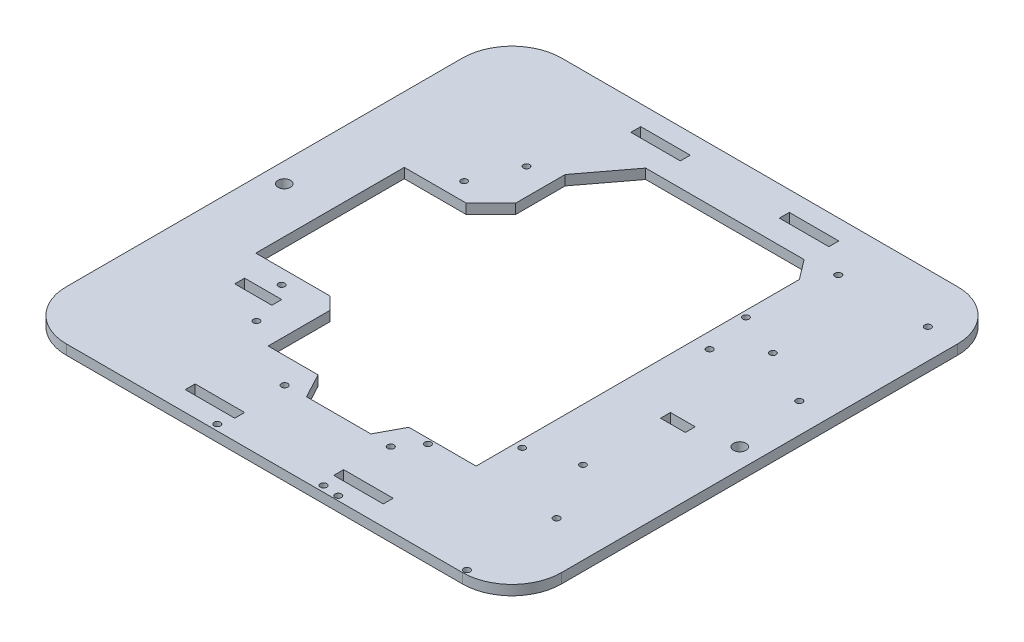
SolidWorks part; units mm, degrees
ref_plane "Front Plane" through (0, 0, 0) normal (0, 0, 1) x (1, 0, 0)
ref_plane "Top Plane" through (0, 0, 0) normal (0, 1, 0) x (1, 0, 0)
ref_plane "Right Plane" through (0, 0, 0) normal (1, 0, 0) x (0, 0, -1)
sketch "Sketch1" plane through (0, 0, 0) normal (0, 1, 0) x (1, 0, 0)
  line L1 (-127, -127) -> (127, -127)
  line L2 (-127, -127) -> (-127, 127)
  line L3 (-127, 127) -> (127, 127)
  line L4 (127, -127) -> (127, 127)
  line L5 (-127, -127) -> (127, 127) construction
  line L6 (-127, 127) -> (127, -127) construction
  point P0 (0, 0)
  dimension "D1" = 254
  dimension "D2" = 254
extrude "Platform-Base" add sketch "Sketch1" along normal blind 5.08
ref_axis "Axis1" through (-127, 5.08, 0) along (0, -1, 0)
ref_plane "Plane1" through (0, 0, 0) normal (0, 0, 1) x (0, -1, 0)
sketch "Sketch5" plane through (0, 5.08, 0) normal (0, 1, 0) x (1, 0, 0)
  line L0 (127, 0) -> (0, 0) construction
  line L1 (127, -127) -> (127, 127) construction
  line L3 (48.895, 76.2) -> (-48.895, 76.2)
  line L4 (48.895, 76.2) -> (48.895, -76.2)
  line L5 (48.895, -76.2) -> (-48.895, -76.2)
  line L6 (-48.895, 76.2) -> (-48.895, -76.2)
  line L7 (48.895, 76.2) -> (-48.895, -76.2) construction
  line L8 (48.895, -76.2) -> (-48.895, 76.2) construction
  dimension "D1" = 127
  dimension "D2" = 97.79
  dimension "D3" = 152.4
extrude "Cut-Extrude3" cut sketch "Sketch5" against normal through all
sketch "Sketch6" plane through (0, 5.08, 0) normal (0, 1, 0) x (1, 0, 0)
  line L2 (25.4, -116.84) -> (25.4, -127) construction
  line L3 (-127, -127) -> (127, -127) construction
  line L4 (50.8, -116.84) -> (127, -116.84) construction
  line L5 (25.4, -116.84) -> (50.8, -116.84)
  line L6 (25.4, -116.84) -> (25.4, -111.76)
  line L7 (25.4, -111.76) -> (50.8, -111.76)
  line L8 (50.8, -116.84) -> (50.8, -111.76)
  line L9 (127, -127) -> (127, 127) construction
  dimension "D2" = 10.16
  dimension "D3" = 5.08
extrude "Cut-Extrude4" cut sketch "Sketch6" against normal through all
mirror "Mirror4" about plane through (0, 0, 0) normal (0, 0, 1) of "Cut-Extrude4"
fillet "Corner-Rounding" radius 25.4 4 edges at (-127, 2.54, -127) (127, 2.54, -127) (127, 2.54, 127) (-127, 2.54, 127)
ref_axis "Axis2" through (0, 5.08, 127) along (0, -1, 0)
ref_plane "Plane2" through (0, 0, 0) normal (-1, 0, 0) x (0, -1, 0)
mirror "Mirror6" about plane through (0, 0, 0) normal (-1, 0, 0) of "Mirror4"
sketch "Sketch7" plane through (0, 5.08, 0) normal (0, 1, 0) x (1, 0, 0)
  line L0 (127, 0) -> (116.84, 0) construction
  line L1 (127, -101.6) -> (127, 101.6) construction
  circle A0 centre (116.84, 0) radius 3.175
  dimension "D1" = 6.35
  dimension "D2" = 10.16
extrude "Cut-Extrude5" cut sketch "Sketch7" against normal through all
mirror "Mirror7" about plane through (0, 0, 0) normal (-1, 0, 0) of "Cut-Extrude5"
sketch "Sketch11" plane through (0, 5.08, 0) normal (0, 1, 0) x (1, 0, 0)
  line L0 (127, -5.08) -> (127, 0) construction
  line L1 (127, -101.6) -> (127, 101.6) construction
  line L2 (127, -5.08) -> (90.17, -5.08) construction
  line L4 (83.82, -7.62) -> (96.52, -7.62)
  line L5 (83.82, -7.62) -> (83.82, -2.54)
  line L6 (83.82, -2.54) -> (96.52, -2.54)
  line L7 (96.52, -7.62) -> (96.52, -2.54)
  line L8 (83.82, -7.62) -> (96.52, -2.54) construction
  line L9 (83.82, -2.54) -> (96.52, -7.62) construction
  dimension "D3" = 5.08
  dimension "D2" = 36.83
extrude "Cut-Extrude8" cut sketch "Sketch11" against normal through all
sketch "Sketch12" plane through (0, 5.08, 0) normal (0, 1, 0) x (1, 0, 0)
  line L0 (-66.04, -127) -> (-66.04, -57.15) construction
  line L1 (-101.6, -127) -> (101.6, -127) construction
  line L2 (-66.04, -57.15) -> (-127, -57.15) construction
  line L3 (-127, 101.6) -> (-127, -101.6) construction
  line L5 (-66.04, -57.15) -> (-85.09, -57.15)
  line L6 (-66.04, -57.15) -> (-66.04, -52.07)
  line L7 (-66.04, -52.07) -> (-85.09, -52.07)
  line L8 (-85.09, -57.15) -> (-85.09, -52.07)
  dimension "D1" = 69.85
  dimension "D2" = 60.96
  dimension "D3" = 19.05
  dimension "D4" = 5.08
extrude "Cut-Extrude10" cut sketch "Sketch12" against normal blind 16.51
sketch "Sketch14" plane through (48.895, 0, 0) normal (-1, 0, 0) x (0, 0, 1)
  line L0 (0, 5.08) -> (0, 2.1293) construction
  line L1 (76.2, 5.08) -> (-76.2, 5.08) construction
  line L3 (-76.2, -0.4107) -> (76.2, -0.4107)
  line L4 (-76.2, -0.4107) -> (-76.2, 7.62)
  line L5 (-76.2, 7.62) -> (76.2, 7.62)
  line L6 (76.2, -0.4107) -> (76.2, 7.62)
  line L7 (-76.2, -0.4107) -> (76.2, 7.62) construction
  line L8 (-76.2, 7.62) -> (76.2, -0.4107) construction
  point P5 (0, 3.6047)
  dimension "D1" = 152.4
extrude "Cut-Extrude12" cut sketch "Sketch14" against normal blind 19.05
sketch "Sketch16" plane through (-48.895, 0, 0) normal (1, 0, 0) x (0, 0, -1)
  line L0 (0, 5.08) -> (0, 0) construction
  line L1 (76.2, 5.08) -> (-76.2, 5.08) construction
  line L2 (76.2, 0) -> (-76.2, 0) construction
  line L4 (-38.1, 5.08) -> (38.1, 5.08)
  line L5 (-38.1, 5.08) -> (-38.1, 0)
  line L6 (-38.1, 0) -> (38.1, 0)
  line L7 (38.1, 5.08) -> (38.1, 0)
  line L8 (-38.1, 5.08) -> (38.1, 0) construction
  line L9 (-38.1, 0) -> (38.1, 5.08) construction
  point P6 (0, 2.54)
  dimension "D1" = 76.2
extrude "Cut-Extrude14" cut sketch "Sketch16" against normal blind 44.45
sketch "Sketch18" plane through (0, 5.08, 0) normal (0, 1, 0) x (1, 0, 0)
  line L6 (-48.895, 76.2) -> (-26.6168, 34.3809)
  line L8 (-48.895, 76.2) -> (-31.115, 99.6865)
  line L9 (-31.115, 99.6865) -> (50.165, 99.6865)
  line L10 (67.945, 76.2) -> (50.165, 99.6865)
  line L11 (101.6, 127) -> (-101.6, 127) construction
  line L12 (-26.6168, 34.3809) -> (67.945, 76.2)
  dimension "D1" = 81.28
extrude "Cut-Extrude16" cut sketch "Sketch18" against normal through all
sketch "Sketch20" plane through (0, 5.08, 0) normal (0, 1, 0) x (1, 0, 0)
  line L0 (-48.895, 38.1) -> (-48.895, 50.8)
  line L1 (-48.895, 76.2) -> (-48.895, 38.1) construction
  line L2 (-48.895, 50.8) -> (-61.595, 38.1)
  line L3 (-93.345, 38.1) -> (-48.895, 38.1) construction
  line L4 (-61.595, 38.1) -> (-48.895, 38.1)
  dimension "D1" = 12.7
extrude "Cut-Extrude18" cut sketch "Sketch20" against normal through all
sketch "Sketch21" plane through (0, 5.08, 0) normal (0, 1, 0) x (1, 0, 0)
  line L0 (-48.895, -38.1) -> (-48.895, -44.45)
  line L1 (-48.895, -38.1) -> (-48.895, -76.2) construction
  line L2 (-48.895, -44.45) -> (-55.245, -38.1)
  line L3 (-93.345, -38.1) -> (-48.895, -38.1) construction
  line L4 (-55.245, -38.1) -> (-48.895, -38.1)
  dimension "D1" = 6.35
extrude "Cut-Extrude19" cut sketch "Sketch21" against normal through all
sketch "Sketch22" plane through (0, 5.08, 0) normal (0, 1, 0) x (1, 0, 0)
  line L0 (-25.4, -111.76) -> (25.4, -111.76) construction
  line L1 (25.4, -111.76) -> (25.4, -116.84) construction
  line L2 (50.8, -111.76) -> (25.4, -111.76) construction
  line L3 (0, -111.76) -> (0, -88.9) construction
  line L4 (0, -88.9) -> (16.51, -88.9)
  line L5 (16.51, -88.9) -> (23.2939, -76.2)
  line L6 (-48.895, -76.2) -> (67.945, -76.2) construction
  line L7 (0, -88.9) -> (-16.51, -88.9)
  line L8 (-16.51, -88.9) -> (-23.2939, -76.2)
  line L9 (-23.2939, -76.2) -> (-5.6383, -47.7846)
  line L10 (-5.6383, -47.7846) -> (23.2939, -76.2)
  dimension "D1" = 22.86
  dimension "D2" = 16.51
extrude "Cut-Extrude20" cut sketch "Sketch22" against normal through all
sketch "Sketch27" plane through (0, 0, 76.2) normal (0, 0, -1) x (-1, 0, 0)
  line L0 (-23.2939, 5.08) -> (-67.945, 5.08) construction
  line L1 (-57.785, 5.08) -> (-67.945, 5.08)
  line L2 (-57.785, 5.08) -> (-57.785, 0)
  line L3 (-57.785, 0) -> (-67.945, 0)
  line L4 (-67.945, 5.08) -> (-67.945, 0)
  dimension "D1" = 10.16
extrude "Boss-Extrude1" add sketch "Sketch27" along normal blind 177.8
sketch "Sketch28" plane through (0, 0, 0) normal (0, -1, 0) x (1, 0, 0)
  circle A0 centre (-62.9935, 68.1005) radius 1.6
  circle A1 centre (-72.5993, 45.5914) radius 1.6
  circle A2 centre (-71.8559, -47.2939) radius 1.6
  circle A3 centre (-62.447, -69.886) radius 1.6
  circle A4 centre (60.9077, -59.1041) radius 1.6
  circle A5 centre (83.6846, -50.152) radius 1.6
  circle A6 centre (84.632, 48.2516) radius 1.6
  circle A7 centre (61.5077, 56.2638) radius 1.6
extrude "Cut-Extrude22" cut sketch "Sketch28" against normal through all
sketch "Sketch29" plane through (0, 5.08, 0) normal (0, 1, 0) x (1, 0, 0)
  line L0 (0, -127) -> (0, -106.68) construction
  line L1 (-101.6, -127) -> (101.6, -127) construction
  line L3 (27.25, -89.43) -> (-27.25, -89.43) construction
  line L4 (27.25, -89.43) -> (27.25, -123.93) construction
  line L5 (27.25, -123.93) -> (-27.25, -123.93) construction
  line L6 (-27.25, -89.43) -> (-27.25, -123.93) construction
  line L7 (27.25, -89.43) -> (-27.25, -123.93) construction
  line L8 (27.25, -123.93) -> (-27.25, -89.43) construction
  circle A0 centre (-27.25, -123.93) radius 1.651
  circle A1 centre (-27.25, -89.43) radius 1.651
  circle A2 centre (27.25, -89.43) radius 1.651
  circle A3 centre (27.25, -123.93) radius 1.651
  dimension "D1" = 3.302
  dimension "D2" = 34.5
  dimension "D3" = 20.32
  dimension "D4" = 54.5
extrude "Cut-Extrude23" cut sketch "Sketch29" against normal through all
sketch "Sketch30" plane through (0, 5.08, 0) normal (0, 1, 0) x (1, 0, 0)
  line L0 (127, -78.74) -> (101.6, -78.74) construction
  line L1 (127, -101.6) -> (127, 101.6) construction
  line L2 (101.6, -78.74) -> (101.6, -127) construction
  line L3 (-101.6, -127) -> (101.6, -127) construction
  line L5 (101.6, -78.74) -> (35.6, -78.74) construction
  line L6 (101.6, -78.74) -> (101.6, -124.74) construction
  line L7 (101.6, -124.74) -> (35.6, -124.74) construction
  line L8 (35.6, -78.74) -> (35.6, -124.74) construction
  circle A0 centre (101.6, -124.74) radius 1.651
  circle A1 centre (35.6, -124.74) radius 1.651
  circle A2 centre (35.6, -78.74) radius 1.651
  circle A3 centre (101.6, -78.74) radius 1.651
  dimension "D3" = 3.302
  dimension "D1" = 25.4
  dimension "D2" = 48.26
  dimension "D4" = 46
  dimension "D5" = 66
extrude "Cut-Extrude24" cut sketch "Sketch30" against normal through all
sketch "Sketch32" plane through (0, 5.08, 0) normal (0, 1, 0) x (1, 0, 0)
  line L0 (88.76, 101.6) -> (88.76, 127) construction
  line L1 (65.76, 35.6) -> (111.76, 35.6) construction
  line L2 (65.76, 35.6) -> (65.76, 101.6) construction
  line L3 (65.76, 101.6) -> (111.76, 101.6) construction
  line L4 (111.76, 35.6) -> (111.76, 101.6) construction
  line L6 (101.6, 127) -> (-101.6, 127) construction
  line L7 (111.76, 68.6) -> (127, 68.6) construction
  line L8 (127, -101.6) -> (127, 101.6) construction
  circle A0 centre (65.76, 35.6) radius 1.651
  circle A1 centre (111.76, 35.6) radius 1.651
  circle A2 centre (111.76, 101.6) radius 1.651
  circle A3 centre (65.76, 101.6) radius 1.651
  dimension "D3" = 3.302
  dimension "D1" = 25.4
  dimension "D2" = 15.24
  dimension "D4" = 66
  dimension "D5" = 46
extrude "Cut-Extrude26" cut sketch "Sketch32" against normal through all
equation "\"Foamcore\" = .1in"
equation "\"MDF\" = .2in"
equation "\"Gmaterial\"= \"MDF\""
equation "\"D1@Platform-Base\" = \"Gmaterial\""
equation "\"D3@Sketch6\"=\"Gmaterial\""
equation "\"D3@Sketch11\"=\"Gmaterial\""
equation "\"D3@Sketch12\"=.75"
equation "\"D1@Sketch11\"=\"Gmaterial\""
equation "\"D4@Sketch12\"=\"Gmaterial\""
